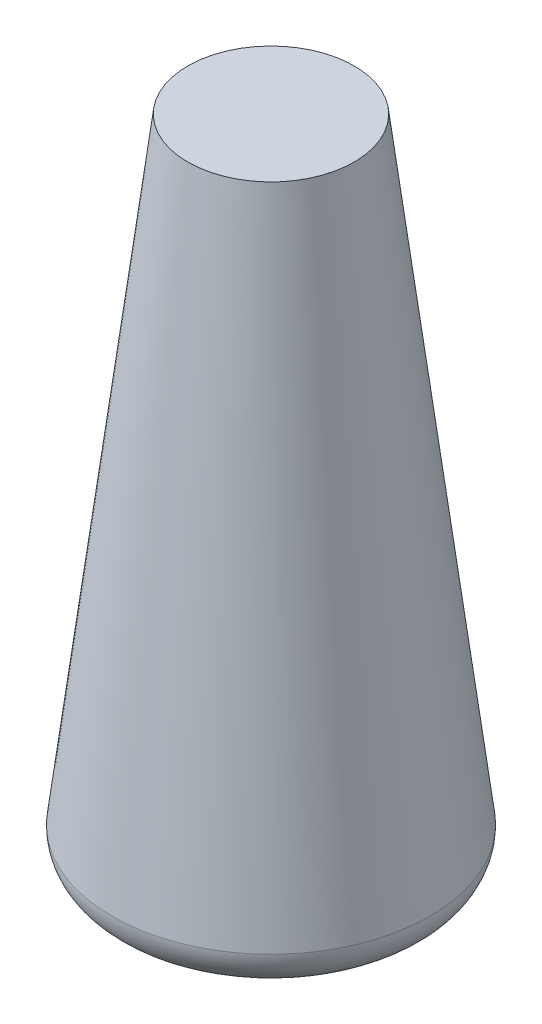
SolidWorks part; units mm, degrees
ref_plane "Front Plane" through (0, 0, 0) normal (0, 0, 1) x (1, 0, 0)
ref_plane "Top Plane" through (0, 0, 0) normal (0, 1, 0) x (1, 0, 0)
ref_plane "Right Plane" through (0, 0, 0) normal (1, 0, 0) x (0, 0, -1)
sketch "Sketch2" plane through (0, 0, 0) normal (0, 1, 0) x (1, 0, 0)
  circle A0 centre (0, 0) radius 40
  dimension "D1" = 80
extrude "Boss-Extrude2" add sketch "Sketch2" along normal blind 10
sketch "Sketch3" plane through (0, 10, 0) normal (0, 1, 0) x (1, 0, 0)
  circle A1 centre (0, 0) radius 40
  circle A2 centre (0, 0) radius 40
  dimension "D1" = 0
extrude "Boss-Extrude4" add sketch "Sketch3" along normal blind 155 draft 7
fillet "Fillet4" radius 10 1 edges at (0, 0, 40)
